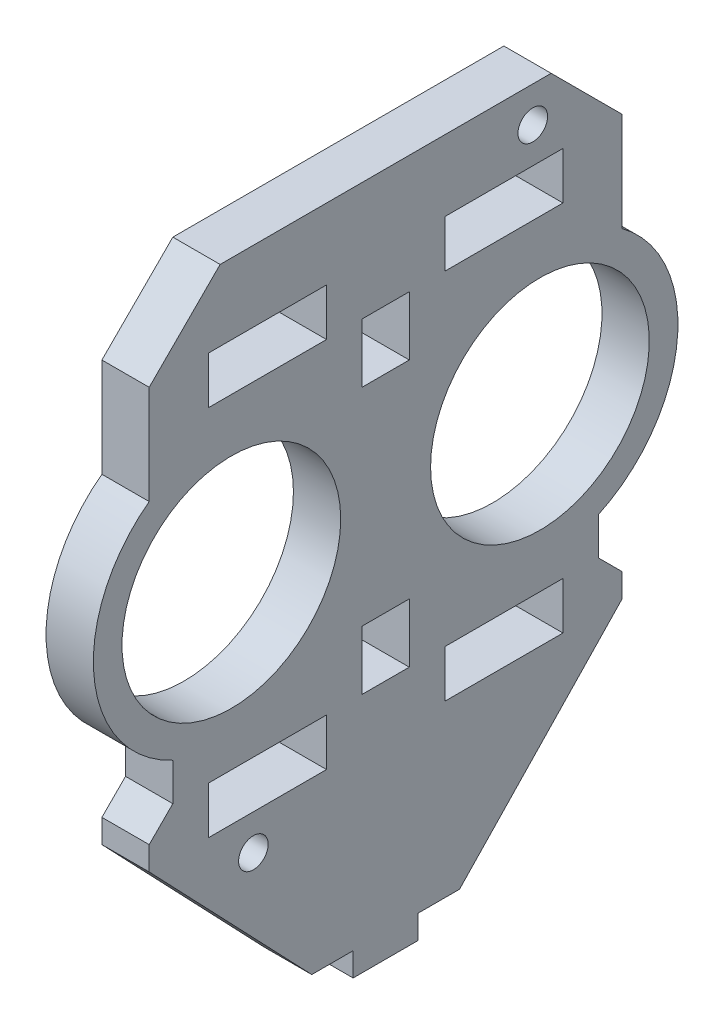
SolidWorks part; units mm, degrees
ref_plane "Front Plane" through (0, 0, 0) normal (0, 0, 1) x (1, 0, 0)
ref_plane "Top Plane" through (0, 0, 0) normal (0, 1, 0) x (1, 0, 0)
ref_plane "Right Plane" through (0, 0, 0) normal (1, 0, 0) x (0, 0, -1)
sketch "Sketch1" plane through (0, 0, 0) normal (1, 0, 0) x (0, 0, -1)
  line L0 (0, 86.3618) -> (0, -95.6447) construction
  line L1 (-34.45, 0) -> (67.35, 0) construction
  line L2 (-12.5, -64.29) -> (-40, -35.5)
  line L3 (-40, -31.5) -> (-40, -35.5)
  line L4 (-40, -31.5) -> (-36, -27.5)
  line L5 (-12.5, -64.29) -> (-12.5, -68.29)
  line L6 (-12.5, -68.29) -> (12.5, -68.29)
  line L7 (12.5, -64.29) -> (12.5, -68.29)
  line L8 (-36, -27.5) -> (-36, -21.1431)
  line L9 (-40, 35.5) -> (-40, 18.7571)
  line L10 (-40, 35.5) -> (-28, 47.5)
  line L11 (40, 35.5) -> (-40, 35.5) construction
  line L12 (40, 35.5) -> (40, 18.7571)
  line L13 (40, -35.5) -> (40, -31.5)
  line L14 (40, -31.5) -> (36, -27.5)
  line L15 (36, -27.5) -> (36, -21.1431)
  line L16 (12.5, -64.29) -> (40, -35.5)
  line L17 (40, -35.5) -> (-40, -35.5) construction
  line L18 (40, 35.5) -> (28, 47.5)
  line L19 (-28, 47.5) -> (28, 47.5)
  line L20 (-40, -35.5) -> (-40, -27.5) construction
  circle A0 centre (0, 0) radius 76.29 construction
  circle A1 centre (-22.3739, -41.5) radius 2.5
  circle A2 centre (24.8916, 41.5) radius 2.5
  circle A3 centre (-26.1, 0) radius 23.3461 construction
  circle A4 centre (-26.1, 0) radius 18.5
  circle A5 centre (26.1, 0) radius 18.5
  circle A6 centre (26.1, 0) radius 23.3461 construction
  arc A9 (-40, 18.7571) -> (-36, -21.1431) centre (-26.1, 0) ccw
  arc A10 (40, 18.7571) -> (36, -21.1431) centre (26.1, 0) cw
  circle A11 centre (-26.1, 0) radius 8.35 construction
  circle A13 centre (70, 0) radius 2.65 construction
  circle A14 centre (-43.3013, -25) radius 7 construction
  point P14 (0, 0)
  point P16 (0, -76.29)
  point P20 (-62.4774, 0)
  point P27 (0, -68.29)
  point P30 (0, 56.7762)
  point P31 (0, 56.7762)
  point P33 (-40, -35.5)
  point P41 (-40, -35.5)
  point P42 (0, 0)
  point P46 (0, 0)
  point P47 (-40, -31.5)
  dimension "D1" = 152.58
  dimension "D2" = 5
  dimension "D5" = 37
  dimension "D9" = 8
  dimension "D7" = 6
  dimension "D10" = 4
  dimension "D3" = 6
  dimension "D4" = 5
  dimension "D6" = 124.9548
  dimension "D8" = 25
  dimension "D11" = 12
  dimension "D12" = 12
  dimension "D15" = 4
extrude "Boss-Extrude1" add sketch "Sketch1" along normal blind 8
sketch "Sketch2" plane through (0, 0, 0) normal (-1, 0, 0) x (0, 0, 1)
  line L0 (0, -90.2636) -> (0, 91.611) construction
  line L1 (-93.4475, 0) -> (84.8595, 0) construction
  line L2 (10, -27.5) -> (10, -35.5)
  line L3 (-30, -27.5) -> (-10, -27.5)
  line L4 (-30, -27.5) -> (-30, -35.5)
  line L5 (-30, -35.5) -> (-10, -35.5)
  line L6 (-10, -27.5) -> (-10, -35.5)
  line L7 (30, -35.5) -> (10, -35.5)
  line L8 (30, -27.5) -> (30, -35.5)
  line L9 (30, -27.5) -> (10, -27.5)
  line L10 (30, 27.5) -> (10, 27.5)
  line L11 (30, 27.5) -> (30, 35.5)
  line L12 (30, 35.5) -> (10, 35.5)
  line L13 (-10, 27.5) -> (-10, 35.5)
  line L14 (-30, 35.5) -> (-10, 35.5)
  line L15 (-30, 27.5) -> (-30, 35.5)
  line L16 (-30, 27.5) -> (-10, 27.5)
  line L17 (10, 27.5) -> (10, 35.5)
  line L18 (4, 17.5) -> (4, 27.5)
  line L19 (-4, -17.5) -> (4, -17.5)
  line L20 (-4, -17.5) -> (-4, -27.5)
  line L21 (-4, -27.5) -> (4, -27.5)
  line L22 (4, -17.5) -> (4, -27.5)
  line L23 (-4, 27.5) -> (4, 27.5)
  line L24 (-4, 17.5) -> (-4, 27.5)
  line L25 (-4, 17.5) -> (4, 17.5)
  line L26 (5.5, -68.29) -> (5.5, -64.29)
  line L27 (-12.5, -68.29) -> (-5.5, -68.29)
  line L28 (-12.5, -68.29) -> (-12.5, -64.29)
  line L29 (-12.5, -64.29) -> (-5.5, -64.29)
  line L30 (-5.5, -68.29) -> (-5.5, -64.29)
  line L31 (12.5, -64.29) -> (5.5, -64.29)
  line L32 (12.5, -68.29) -> (12.5, -64.29)
  line L33 (12.5, -68.29) -> (5.5, -68.29)
  point P26 (0, -17.5)
  dimension "D1" = 27.5
  dimension "D2" = 20
  dimension "D3" = 20
  dimension "D4" = 8
  dimension "D5" = 8
  dimension "D6" = 10
  dimension "D7" = 4
  dimension "D8" = 7
extrude "Cut-Extrude1" cut sketch "Sketch2" against normal up to next
